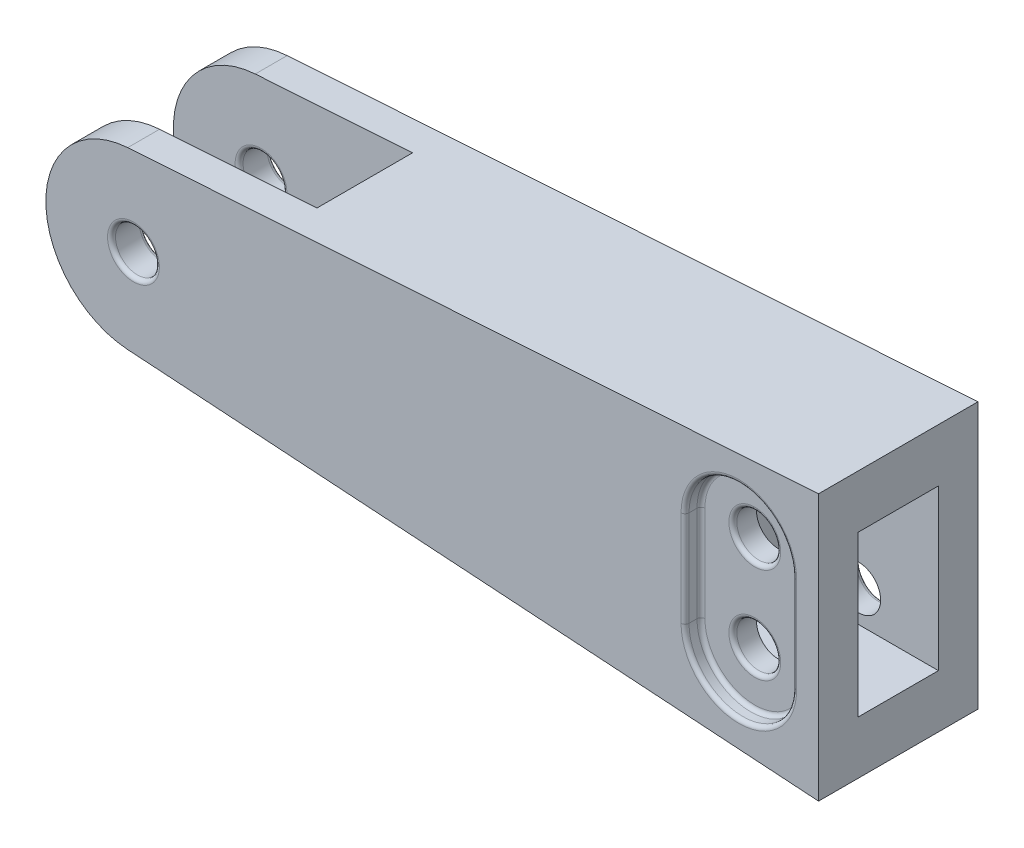
SolidWorks part; units mm, degrees
ref_plane "Front Plane" through (0, 0, 0) normal (0, 0, 1) x (1, 0, 0)
ref_plane "Top Plane" through (0, 0, 0) normal (0, 1, 0) x (1, 0, 0)
ref_plane "Right Plane" through (0, 0, 0) normal (1, 0, 0) x (0, 0, -1)
sketch "Sketch1" plane through (0, 0, 0) normal (0, 0, 1) x (1, 0, 0)
  line L1 (43.0973, 0) -> (50043.0973, 0) construction
  line L2 (0, 21.9801) -> (0, 50021.9801) construction
  line L5 (-147.5823, 10.9688) -> (-60.9249, 16.6957)
  line L6 (-60.9249, -16.6957) -> (-17.5192, -19.5642) construction
  line L7 (-60.9249, 16.6957) -> (-60.9249, -16.6957) construction
  line L8 (-60.9249, 16.6957) -> (-60.9249, -16.6957)
  line L9 (-147.5823, -10.9688) -> (-60.9249, -16.6957)
  arc A1 (-147.5823, 10.9688) -> (-147.5823, -10.9688) centre (-146.8574, 0) ccw
  point P8 (0, 0)
  point P9 (0, 0)
  point P13 (0, 0)
  dimension "D1" = 146.8574
extrude "Boss-Extrude1" add sketch "Sketch1" along normal up to surface (20 mm away) contours A1 region at (-104.6894, 0, 0)
sketch "Sketch2" plane through (-60.9249, 0, 0) normal (1, 0, 0) x (0, 0, -1)
  line L0 (-10, -16.6957) -> (-10, 16.6957) construction
  line L4 (-15.035, -10.035) -> (-4.965, -10.035)
  line L5 (-15.035, -10.035) -> (-15.035, 10.035)
  line L6 (-15.035, 10.035) -> (-4.965, 10.035)
  line L7 (-20, -16.6957) -> (0, -16.6957)
  line L13 (-20, 16.6957) -> (-20, -16.6957)
  line L14 (0, 16.6957) -> (-20, 16.6957)
  line L15 (0, -16.6957) -> (0, 16.6957)
  line L16 (-20, -16.6957) -> (0, -16.6957) construction
  line L17 (-20, 16.6957) -> (-20, -16.6957) construction
  line L18 (0, 16.6957) -> (-20, 16.6957) construction
  line L19 (0, -16.6957) -> (0, 16.6957) construction
  line L20 (-4.965, -10.035) -> (-4.965, 10.035)
  line L21 (-15.035, -10.035) -> (-4.965, 10.035) construction
  line L22 (-15.035, 10.035) -> (-4.965, -10.035) construction
  line L23 (0, 0) -> (-20, 0) construction
  point P2 (-10, 0)
  point P15 (-10, 0)
  dimension "D2" = 10.07
  dimension "D3" = 20.07
  dimension "D1" = 0
extrude "Cut-Extrude1" cut sketch "Sketch2" against normal blind 20
sketch "Sketch4" plane through (0, 0, 0) normal (0, 1, 0) x (1, 0, 0)
  line L0 (-60.9249, -20) -> (-147.5823, -20) construction
  line L5 (-157.8501, 0) -> (-157.8501, -20) construction
  line L6 (-157.8501, -4) -> (-127.8501, -4)
  line L7 (-157.8501, -4) -> (-157.8501, -16)
  line L10 (-157.8501, -16) -> (-127.8501, -16)
  line L15 (-127.8501, -4) -> (-127.8501, -16)
  line L16 (-157.8501, -4) -> (-127.8501, -16) construction
  line L17 (-157.8501, -16) -> (-127.8501, -4) construction
  line L18 (-147.5823, 0) -> (-157.8501, 0) construction
  point P4 (-142.8501, -10)
  dimension "D1" = 4
  dimension "D2" = 4
  dimension "D3" = 30
extrude "Cut-Extrude2" cut sketch "Sketch4" against normal through all both and the other way through all
sketch "Sketch5" plane through (0, 0, 0) normal (0, 0, -1) x (-1, 0, 0)
  circle A0 centre (146.8574, 0) radius 2.75
  dimension "D1" = 5.5
extrude "Cut-Extrude3" cut sketch "Sketch5" against normal through all
sketch "Sketch6" plane through (0, 0, 0) normal (0, 0, -1) x (-1, 0, 0)
  line L1 (0, 0) -> (50000, 0) construction
  line L2 (60.9249, 16.6957) -> (60.9249, -16.6957) construction
  circle A0 centre (70.9249, -6) radius 2.75
  circle A1 centre (70.9249, 6) radius 2.75
  point P4 (70.5734, 6)
  dimension "D1" = 5.5
  dimension "D2" = 10
  dimension "D3" = 6
extrude "Cut-Extrude4" cut sketch "Sketch6" against normal through all
sketch "Sketch8" plane through (0, 0, 0) normal (0, 0, -1) x (-1, 0, 0)
  line L0 (64.1749, 6) -> (64.1749, -6)
  line L2 (77.6749, 6) -> (77.6749, -6)
  circle A0 centre (70.9249, -6) radius 2.75 construction
  circle A1 centre (70.9249, 6) radius 2.75 construction
  circle A2 centre (70.9249, -6) radius 2.75 construction
  circle A3 centre (70.9249, 6) radius 2.75 construction
  arc A4 (64.1749, -6) -> (77.6749, -6) centre (70.9249, -6) ccw
  arc A5 (77.6749, 6) -> (64.1749, 6) centre (70.9249, 6) ccw
  circle A6 centre (70.9249, 6) radius 6.75 construction
  circle A7 centre (70.9249, -6) radius 6.75 construction
  dimension "D1" = 4
extrude "Cut-Extrude5" cut sketch "Sketch8" against normal blind 2
ref_plane "Plane1" through (0, 0, 10) normal (0, 0, -1) x (-1, 0, 0)
mirror "Mirror1" about plane through (0, 0, 10) normal (0, 0, -1) of "Cut-Extrude5"
fillet "Fillet2" radius 0.5 24 edges at (-70.9249, -12.75, 2) (-64.1749, 0, 2) (-70.9249, 12.75, 2) (-70.9249, -12.75, 0) (-64.1749, 0, 0) (-70.9249, 12.75, 0) (-70.9249, -12.75, 18) (-64.1749, 0, 18) (-70.9249, 12.75, 18) (-70.9249, -12.75, 20) (-64.1749, 0, 20) (-70.9249, 12.75, 20) (-149.6074, 0, 4) (-149.6074, 0, 0) (-144.1074, 0, 16) (-149.6074, 0, 20) (-68.1749, -6, 18) (-68.1749, 6, 18) (-73.6749, -6, 2) (-73.6749, 6, 2) (-77.6749, 0, 18) (-77.6749, 0, 20) (-77.6749, 0, 2) (-77.6749, 0, 0)
